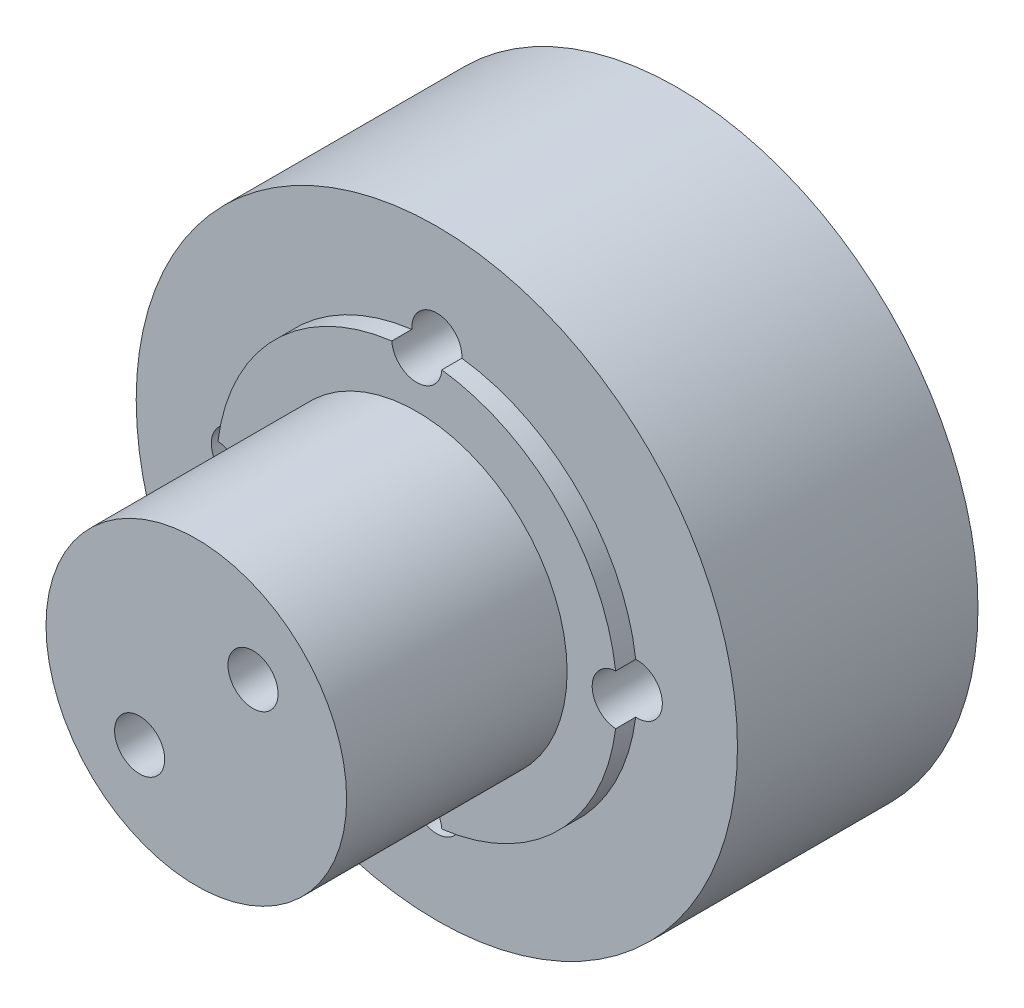
SolidWorks part; units mm, degrees
ref_plane "Спереди" through (0, 0, 0) normal (0, 0, 1) x (1, 0, 0)
ref_plane "Сверху" through (0, 0, 0) normal (0, 1, 0) x (1, 0, 0)
ref_plane "Справа" through (0, 0, 0) normal (1, 0, 0) x (0, 0, -1)
sketch "Эскиз1" plane through (0, 0, 0) normal (0, 0, 1) x (1, 0, 0)
  circle A0 centre (0, 0) radius 15
  dimension "D1" = 30
extrude "Бобышка-Вытянуть1" add sketch "Эскиз1" along normal blind 12
sketch "Эскиз2" plane through (0, 0, 12) normal (0, 0, 1) x (1, 0, 0)
  circle A0 centre (0, 0) radius 10
  dimension "D1" = 20
extrude "Бобышка-Вытянуть2" add sketch "Эскиз2" along normal blind 1
sketch "Эскиз3" plane through (0, 0, 13) normal (0, 0, 1) x (1, 0, 0)
  circle A0 centre (0, 0) radius 7.5
  dimension "D1" = 15
extrude "Бобышка-Вытянуть3" add sketch "Эскиз3" along normal blind 11
sketch "Эскиз4" plane through (0, 0, 0) normal (0, 0, -1) x (-1, 0, 0)
  line L0 (0, 15) -> (0, -15) construction
  line L1 (-15, 0) -> (15, 0) construction
  circle A0 centre (0, 0) radius 15 construction
  circle A1 centre (0, 0) radius 10 construction
  dimension "D1" = 20
hole_wizard "Отверстие обработанное метчиком M3x0.52" positions "Эскиз6" profile "Эскиз5" tap size "M3x0.5" standard "Ansi Metric" end condition through all
sketch "Эскиз6" plane through (0, 0, 0) normal (0, 0, -1) x (-1, 0, 0)
  line L0 (0, 15) -> (0, -15) construction
  line L1 (-15, 0) -> (15, 0) construction
  circle A0 centre (0, 0) radius 10 construction
  point P0 (0, 10)
  point P6 (10, 0)
  point P10 (-10, 0)
  point P12 (0, -10)
sketch "Эскиз5" plane through (0, 10, 0) normal (1, 0, 0) x (0, 1, 0)
  line L0 (0, 0) -> (0, 24)
  line L1 (0, 24) -> (1.25, 24)
  line L2 (1.25, 24) -> (1.25, 0)
  line L5 (1.25, 0) -> (0, 0)
  line L11 (0, -6.35) -> (0, 107.95) construction
  dimension "Диаметр проходного сверла" = 2.5
  dimension "Глубина проходного сверла" = 24
cosmetic thread "Отверстие резьбы1" parameters "D2"=3
cosmetic thread "Отверстие резьбы2" parameters "D2"=3
cosmetic thread "Отверстие резьбы3" parameters "D2"=3
cosmetic thread "Отверстие резьбы4" parameters "D2"=3
sketch "Эскиз7" plane through (0, 0, 24) normal (0, 0, 1) x (1, 0, 0)
  line L0 (2.8284, 2.8284) -> (-2.8284, -2.8284) construction
  line L1 (15, 0) -> (-15, 0) construction
  line L2 (-2.8284, 2.8284) -> (2.8284, -2.8284) construction
  circle A0 centre (0, 0) radius 4 construction
  dimension "D1" = 8
  dimension "D2" = 45
hole_wizard "Отверстие обработанное метчиком M3x0.51" positions "Эскиз9" profile "Эскиз8" tap size "M3x0.5" standard "Ansi Metric"
sketch "Эскиз9" plane through (0, 0, 24) normal (0, 0, 1) x (1, 0, 0)
  point P0 (-2.8284, -2.8284)
  point P3 (2.8284, 2.8284)
cosmetic thread "Отверстие резьбы5" parameters "D1"=8, "D2"=3
cosmetic thread "Отверстие резьбы6" parameters "D1"=8, "D2"=3
sketch "Эскиз8" plane through (-2.8284, -2.8284, 24) normal (1, 0, 0) x (0, -1, 0)
  line L0 (0, 0) -> (0, 8.7511)
  line L1 (0, 8.7511) -> (1.25, 8)
  line L2 (1.25, 8) -> (1.25, 0)
  line L5 (1.25, 0) -> (0, 0)
  line L10 (0, 8.7511) -> (-1.25, 8) construction
  line L11 (0, -6.35) -> (0, 107.95) construction
  dimension "Диаметр сверла" = 2.5
  dimension "Глубина сверла" = 8
  dimension "Угол заточки сверла" = 118
